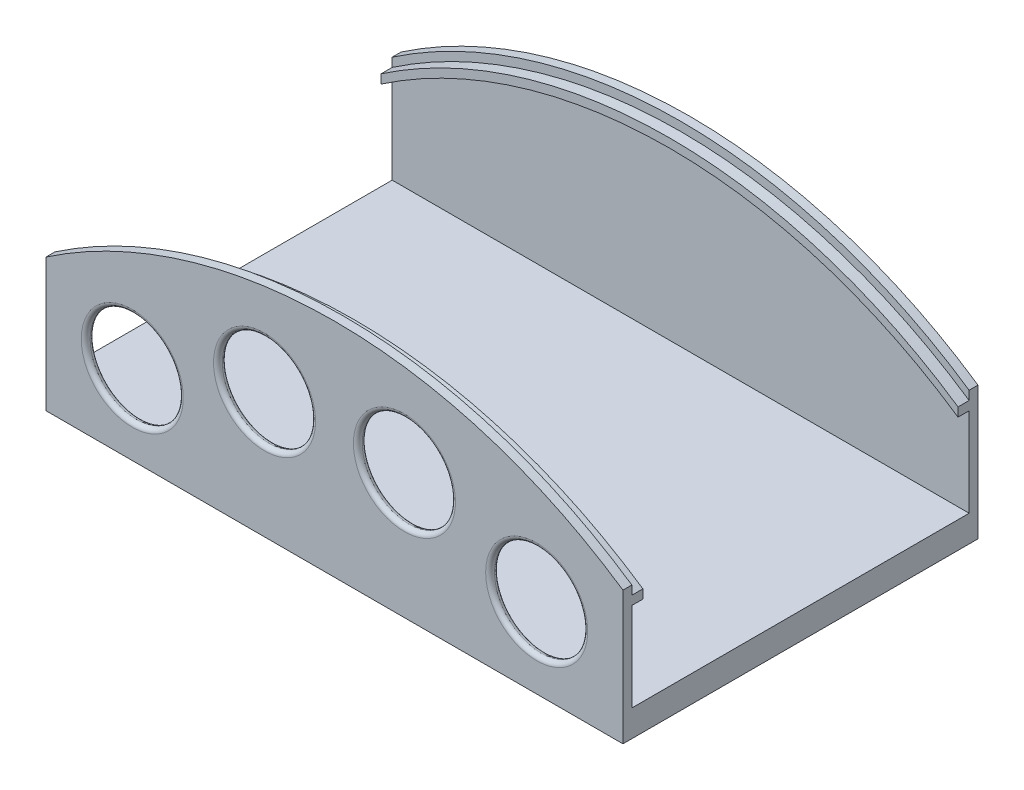
SolidWorks part; units mm, degrees
ref_plane "Спереди" through (0, 0, 0) normal (0, 0, 1) x (1, 0, 0)
ref_plane "Сверху" through (0, 0, 0) normal (0, 1, 0) x (1, 0, 0)
ref_plane "Справа" through (0, 0, 0) normal (1, 0, 0) x (0, 0, -1)
sketch "Эскиз2" plane through (0, 0, 0) normal (0, 0, 1) x (1, 0, 0)
  line L0 (0, 0) -> (130, 0)
  line L1 (130, 0) -> (130, 30)
  line L2 (0, 0) -> (0, 30)
  arc A0 (0, 30) -> (130, 30) centre (65, -65.625) cw
  point P6 (65, 50)
  dimension "D3" = 50
  dimension "D1" = 130
  dimension "D2" = 30
extrude "Бобышка-Вытянуть1" add sketch "Эскиз2" along normal blind 80
sketch "Эскиз3" plane through (130, 0, 0) normal (1, 0, 0) x (0, 0, -1)
  line L0 (0, 0) -> (0, 30) construction
  line L1 (-78, 6) -> (-2, 6)
  line L2 (-78, 6) -> (-78, 56.5661)
  line L3 (-78, 56.5661) -> (-2, 56.5661)
  line L4 (-2, 6) -> (-2, 56.5661)
  line L5 (-80, 0) -> (-80, 30) construction
  line L6 (-80, 0) -> (0, 0) construction
  dimension "D1" = 2
  dimension "D2" = 2
  dimension "D3" = 6
extrude "Вырез-Вытянуть1" cut sketch "Эскиз3" against normal through all
sketch "Эскиз4" plane through (0, 0, 80) normal (0, 0, 1) x (1, 0, 0)
  line L0 (19.4393, 18) -> (49.2373, 28.2923) construction
  line L1 (49.2373, 28.2923) -> (80.7627, 28.2923) construction
  line L2 (80.7627, 28.2923) -> (110.5607, 18) construction
  line L3 (8.9393, 18) -> (0, 18) construction
  line L4 (0, 30) -> (0, 0) construction
  line L5 (121.0607, 18) -> (130, 18) construction
  line L6 (130, 0) -> (130, 30) construction
  line L7 (0, 0) -> (130, 0) construction
  circle A0 centre (19.4393, 18) radius 10.5
  circle A1 centre (49.2373, 28.2923) radius 10.5
  circle A2 centre (80.7627, 28.2923) radius 10.5
  circle A3 centre (110.5607, 18) radius 10.5
  arc A4 (110.5607, 18) -> (19.4393, 18) centre (65, -65.625) ccw construction
  arc A5 (130, 30) -> (0, 30) centre (65, -65.625) ccw construction
  dimension "D1" = 21
  dimension "D3" = 18
extrude "Вырез-Вытянуть2" cut sketch "Эскиз4" against normal up to surface (2 mm away) up to face at (65, 23, 78)
sketch "Эскиз5" plane through (0, 0, 0) normal (0, -1, 0) x (1, 0, 0)
  line L0 (65, 80) -> (65, 0) construction
  line L5 (15, 66) -> (22, 66)
  line L6 (15, 66) -> (15, 14)
  line L7 (0, 80) -> (130, 80) construction
  line L8 (15, 14) -> (22, 14)
  line L9 (22, 66) -> (22, 14)
  line L10 (108, 66) -> (115, 66)
  line L11 (0, 0) -> (130, 0) construction
  line L12 (18.5, 80) -> (18.5, 66) construction
  line L13 (18.5, 14) -> (18.5, 0) construction
  line L14 (108, 66) -> (108, 14)
  line L15 (108, 14) -> (115, 14)
  line L16 (115, 66) -> (115, 14)
  line L17 (0, 40) -> (15, 40) construction
  line L18 (0, 80) -> (0, 0) construction
  dimension "D1" = 52
  dimension "D2" = 7
  dimension "D3" = 15
extrude "Вырез-Вытянуть3" cut sketch "Эскиз5" against normal blind 3.2
fillet "Скругление4" radius 1 8 edges at (121.0607, 18, 80) (121.0607, 18, 78) (91.2627, 28.2923, 80) (91.2627, 28.2923, 78) (59.7373, 28.2923, 80) (59.7373, 28.2923, 78) (29.9393, 18, 80) (29.9393, 18, 78)
sketch "Эскиз7" plane through (0, 0, 78) normal (0, 0, -1) x (-1, 0, 0)
  line L0 (-130, 28) -> (-130, 26) construction
  line L1 (0, 26) -> (0, 28)
  line L2 (0, 30) -> (0, 6) construction
  line L3 (-130, 30) -> (-130, 6) construction
  line L4 (-130, 26) -> (-130, 28)
  arc A0 (-130, 28) -> (0, 28) centre (-65, -67.625) cw
  arc A1 (-130, 26) -> (0, 26) centre (-65, -69.625) cw
  dimension "D1" = 2
  dimension "D2" = 115.625
  dimension "D3" = 2
  dimension "D4" = 2
extrude "Бобышка-Вытянуть2" add sketch "Эскиз7" along normal blind 2.5
sketch "Эскиз9" plane through (0, 0, 2) normal (0, 0, 1) x (1, 0, 0)
  line L0 (0, 6) -> (0, 30) construction
  line L1 (130, 6) -> (130, 30) construction
  line L2 (0, 26) -> (0, 28)
  line L3 (130, 26) -> (130, 28)
  arc A0 (0, 28) -> (130, 28) centre (65, -67.625) cw
  arc A1 (0, 26) -> (130, 26) centre (65, -69.625) cw
  dimension "D2" = 115.625
  dimension "D1" = 2
  dimension "D3" = 2
  dimension "D4" = 2
extrude "Бобышка-Вытянуть3" add sketch "Эскиз9" along normal blind 2.5
